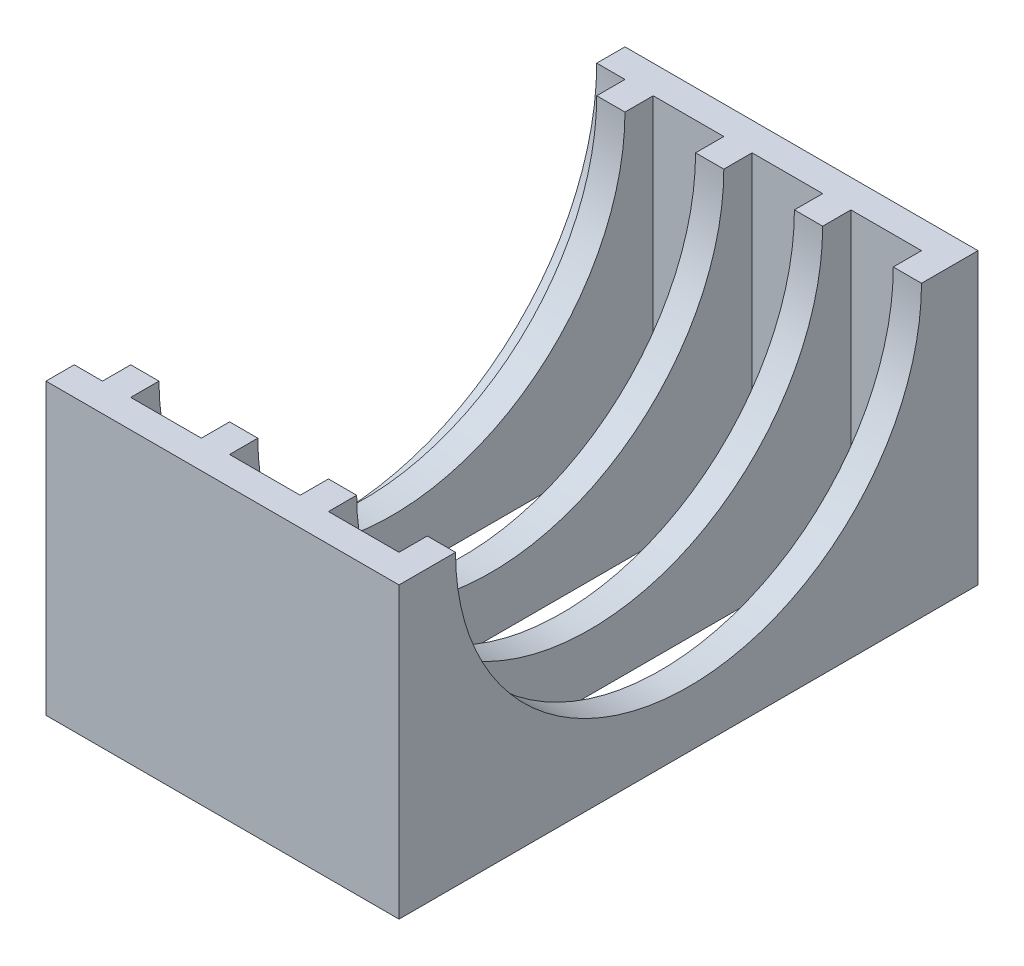
SolidWorks part; units mm, degrees
ref_plane "前视基准面" through (0, 0, 0) normal (0, 0, 1) x (1, 0, 0)
ref_plane "上视基准面" through (0, 0, 0) normal (0, 1, 0) x (1, 0, 0)
ref_plane "右视基准面" through (0, 0, 0) normal (1, 0, 0) x (0, 0, -1)
sketch "草图1" plane through (0, 0, 0) normal (0, 1, 0) x (1, 0, 0)
  line L1 (0, 0) -> (25, 0)
  line L2 (0, 0) -> (0, 41)
  line L3 (0, 41) -> (25, 41)
  line L4 (25, 0) -> (25, 41)
  dimension "D1" = 41
  dimension "D2" = 25
extrude "基座" add sketch "草图1" along normal blind 2
sketch "草图5" plane through (0, 2, 0) normal (0, 1, 0) x (1, 0, 0)
  line L0 (25, 0) -> (25, 41) construction
  line L1 (0, 41) -> (25, 41)
  line L2 (0, 41) -> (0, 39)
  line L3 (0, 39) -> (25, 39)
  line L4 (25, 41) -> (25, 39)
  line L6 (0, 0) -> (25, 0)
  line L7 (0, 0) -> (0, 2)
  line L8 (0, 2) -> (25, 2)
  line L9 (25, 0) -> (25, 2)
  dimension "D1" = 2
  dimension "D2" = 2
extrude "加固" add sketch "草图5" along normal blind 18.5
sketch "草图7" plane through (0, 2, 0) normal (0, 1, 0) x (1, 0, 0)
  line L0 (4, 41) -> (4, 0)
  line L1 (25, 41) -> (0, 41) construction
  line L2 (9, 41) -> (9, -0.7416)
  line L3 (0, 39) -> (0, 2) construction
  line L4 (11, 41) -> (11, 0)
  line L5 (16, 0) -> (16, 41)
  line L6 (0, 0) -> (25, 0) construction
  line L7 (18, 41) -> (18, 0)
  line L8 (23, 41) -> (23, 0)
  line M7 (0, 2) -> (25, 2)
  line M8 (25, 2) -> (25, 39)
  line M9 (25, 39) -> (0, 39)
  line M10 (0, 39) -> (0, 2)
  dimension "D1" = 4
  dimension "D2" = 5
  dimension "D3" = 2
  dimension "D4" = 5
  dimension "D5" = 2
  dimension "D6" = 5
extrude "支架" add sketch "草图7" along normal blind 18.5 contours L0 M9 M10 M7 | L4 L2 M9 M7 | L7 L5 M9 M7 | L8 M9 M7 M8 region at (2, 2, -20.5) region at (10, 2, -20.5) region at (17, 2, -20.5) region at (24, 2, -20.5)
sketch "草图8" plane through (0, 0, 0) normal (-1, 0, 0) x (0, 0, 1)
  line L0 (-41, 20.5) -> (0, 20.5) construction
  circle A0 centre (-20.5, 20.5) radius 18.5
  dimension "D1" = 37
extrude "开口（大）" cut sketch "草图8" against normal blind 2
sketch "草图9" plane through (25, 0, 0) normal (1, 0, 0) x (0, 0, -1)
  line L0 (0, 20.5) -> (41, 20.5) construction
  circle A0 centre (20.5, 20.5) radius 16.5
  dimension "D1" = 33
extrude "开口（小）" cut sketch "草图9" against normal blind 23
sketch "草图10" plane through (0, 2, 0) normal (0, 1, 0) x (1, 0, 0)
  line L1 (4, 39) -> (9, 39)
  line L2 (4, 39) -> (4, 2)
  line L3 (4, 2) -> (9, 2)
  line L4 (9, 39) -> (9, 2)
  line L5 (11, 39) -> (16, 39)
  line L6 (11, 39) -> (11, 2)
  line L7 (11, 2) -> (16, 2)
  line L8 (16, 39) -> (16, 2)
  line L9 (18, 39) -> (23, 39)
  line L10 (18, 39) -> (18, 2)
  line L11 (18, 2) -> (23, 2)
  line L12 (23, 39) -> (23, 2)
extrude "散热口" cut sketch "草图10" against normal blind 2
